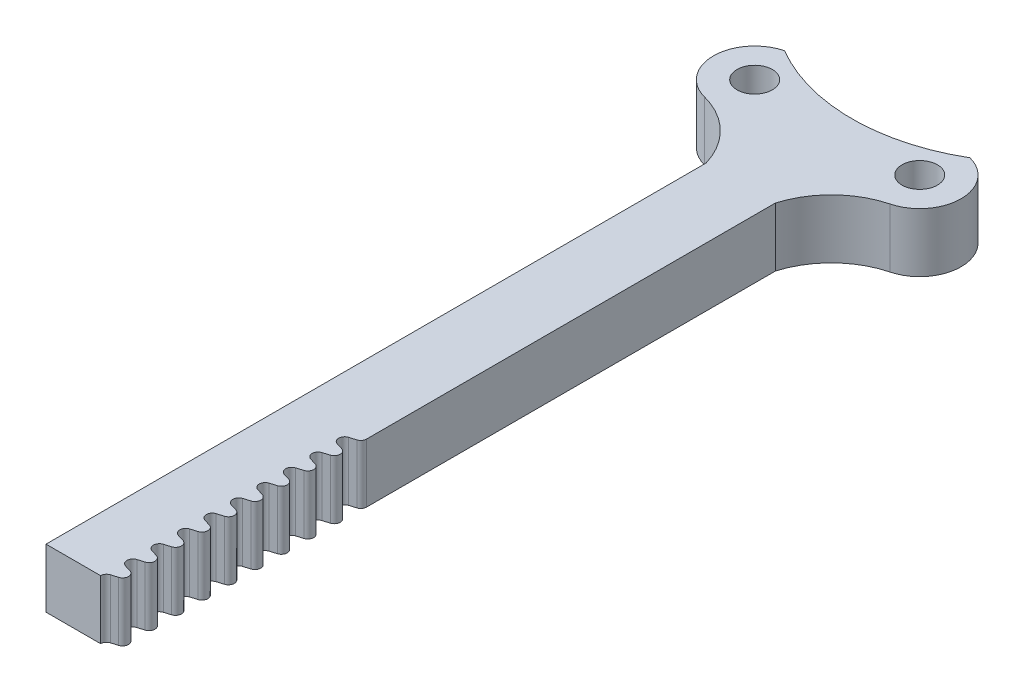
SolidWorks part; units mm, degrees
ref_plane "Plan de face" through (0, 0, 0) normal (0, 0, 1) x (1, 0, 0)
ref_plane "Plan de dessus" through (0, 0, 0) normal (0, 1, 0) x (1, 0, 0)
ref_plane "Plan de droite" through (0, 0, 0) normal (1, 0, 0) x (0, 0, -1)
sketch "Esquisse1" plane through (0, 0, 0) normal (0, 1, 0) x (1, 0, 0)
  line L0 (0, 14.957) -> (0, -16.4348) construction
  line L2 (1.688, -65) -> (-2.938, -65)
  line L4 (-2.938, -65) -> (-2.938, -9.0085)
  line L5 (6.6355, -65) -> (-5.5878, -65) construction
  line L7 (2.0418, -64.5218) -> (2.5842, -64.356)
  line L8 (2.0418, -63.2339) -> (2.5842, -63.3997)
  line L9 (2.0418, -62.2776) -> (2.5842, -62.1118)
  line L10 (2.0418, -60.9897) -> (2.5842, -61.1555)
  line L11 (2.0418, -60.0333) -> (2.5842, -59.8675)
  line L12 (2.0418, -58.7454) -> (2.5842, -58.9112)
  line L13 (2.0418, -57.7891) -> (2.5842, -57.6233)
  line L14 (2.0418, -56.5012) -> (2.5842, -56.667)
  line L15 (2.0418, -55.5449) -> (2.5842, -55.379)
  line L16 (2.0418, -54.2569) -> (2.5842, -54.4227)
  line L17 (2.0418, -53.3006) -> (2.5842, -53.1348)
  line L18 (2.0418, -52.0127) -> (2.5842, -52.1785)
  line L19 (2.0418, -51.0564) -> (2.5842, -50.8905)
  line L20 (2.0418, -49.7684) -> (2.5842, -49.9342)
  line L21 (2.0418, -48.8121) -> (2.5842, -48.6463)
  line L22 (2.0418, -47.5242) -> (2.5842, -47.69)
  line L23 (2.0418, -46.5679) -> (2.5842, -46.402)
  line L24 (2.0418, -45.2799) -> (2.5842, -45.4457)
  line L25 (2.0418, -44.3236) -> (2.5842, -44.1578)
  line L26 (2.938, -43.6796) -> (2.938, -9.0085)
  arc A0 (7.8843, -4.2127) -> (7.8623, 2.5659) centre (7, -0.8262) ccw
  circle A1 centre (7, -0.8262) radius 1.5
  arc A2 (2.0418, -64.5218) -> (1.688, -65) centre (2.188, -65) ccw
  arc A3 (-7.8623, 2.5659) -> (7.8623, 2.5659) centre (0, 15.9238) ccw
  arc A5 (7.8843, -4.2127) -> (2.938, -9.0085) centre (9.653, -10.9855) ccw
  arc A6 (2.5842, -64.356) -> (2.938, -63.8779) centre (2.438, -63.8779) ccw
  arc A8 (-7.8843, -4.2127) -> (-2.938, -9.0085) centre (-9.653, -10.9855) cw
  circle A9 centre (-7, -0.8262) radius 1.5
  arc A10 (-7.8843, -4.2127) -> (-7.8623, 2.5659) centre (-7, -0.8262) cw
  arc A11 (2.5842, -62.1118) -> (2.938, -61.6336) centre (2.438, -61.6336) ccw
  arc A12 (2.938, -63.8779) -> (2.5842, -63.3997) centre (2.438, -63.8779) ccw
  arc A13 (2.0418, -62.2776) -> (2.0418, -63.2339) centre (2.188, -62.7558) ccw
  arc A14 (2.5842, -59.8675) -> (2.938, -59.3894) centre (2.438, -59.3894) ccw
  arc A15 (2.938, -61.6336) -> (2.5842, -61.1555) centre (2.438, -61.6336) ccw
  arc A16 (2.0418, -60.0333) -> (2.0418, -60.9897) centre (2.188, -60.5115) ccw
  arc A17 (2.5842, -57.6233) -> (2.938, -57.1451) centre (2.438, -57.1451) ccw
  arc A18 (2.938, -59.3894) -> (2.5842, -58.9112) centre (2.438, -59.3894) ccw
  arc A19 (2.0418, -57.7891) -> (2.0418, -58.7454) centre (2.188, -58.2673) ccw
  arc A20 (2.5842, -55.379) -> (2.938, -54.9009) centre (2.438, -54.9009) ccw
  arc A21 (2.938, -57.1451) -> (2.5842, -56.667) centre (2.438, -57.1451) ccw
  arc A22 (2.0418, -55.5449) -> (2.0418, -56.5012) centre (2.188, -56.023) ccw
  arc A23 (2.5842, -53.1348) -> (2.938, -52.6566) centre (2.438, -52.6566) ccw
  arc A24 (2.938, -54.9009) -> (2.5842, -54.4227) centre (2.438, -54.9009) ccw
  arc A25 (2.0418, -53.3006) -> (2.0418, -54.2569) centre (2.188, -53.7788) ccw
  arc A26 (2.5842, -50.8905) -> (2.938, -50.4124) centre (2.438, -50.4124) ccw
  arc A27 (2.938, -52.6566) -> (2.5842, -52.1785) centre (2.438, -52.6566) ccw
  arc A28 (2.0418, -51.0564) -> (2.0418, -52.0127) centre (2.188, -51.5345) ccw
  arc A29 (2.5842, -48.6463) -> (2.938, -48.1681) centre (2.438, -48.1681) ccw
  arc A30 (2.938, -50.4124) -> (2.5842, -49.9342) centre (2.438, -50.4124) ccw
  arc A31 (2.0418, -48.8121) -> (2.0418, -49.7684) centre (2.188, -49.2903) ccw
  arc A32 (2.5842, -46.402) -> (2.938, -45.9239) centre (2.438, -45.9239) ccw
  arc A33 (2.938, -48.1681) -> (2.5842, -47.69) centre (2.438, -48.1681) ccw
  arc A34 (2.0418, -46.5679) -> (2.0418, -47.5242) centre (2.188, -47.046) ccw
  arc A35 (2.5842, -44.1578) -> (2.938, -43.6796) centre (2.438, -43.6796) ccw
  arc A36 (2.938, -45.9239) -> (2.5842, -45.4457) centre (2.438, -45.9239) ccw
  arc A37 (2.0418, -44.3236) -> (2.0418, -45.2799) centre (2.188, -44.8018) ccw
  dimension "D1" = 7
  dimension "D2" = 3
  dimension "D3" = 7
  dimension "D4" = 65
  dimension "D7" = 16.75
  dimension "D5" = 7
  dimension "D8" = 31
  dimension "D10" = 0.5
  dimension "D9" = 10
extrude "Boss.-Extru.1" add sketch "Esquisse1" along normal blind 2.5 and the other way blind 2.5
